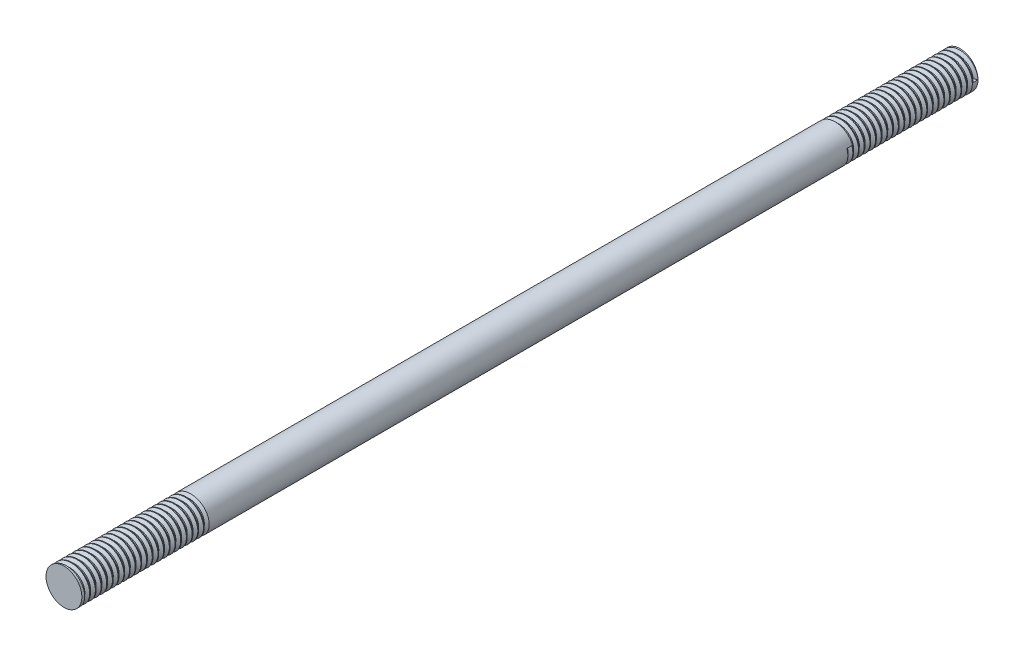
SolidWorks part; units mm, degrees
ref_plane "前视基准面" through (0, 0, 0) normal (0, 0, 1) x (1, 0, 0)
ref_plane "上视基准面" through (0, 0, 0) normal (0, 1, 0) x (1, 0, 0)
ref_plane "右视基准面" through (0, 0, 0) normal (1, 0, 0) x (0, 0, -1)
sketch "草图1" plane through (0, 0, 0) normal (0, 0, 1) x (1, 0, 0)
  circle A0 centre (0, 0) radius 1
  dimension "D1" = 2
extrude "凸台-拉伸1" add sketch "草图1" along normal blind 50
thread "螺纹线1" pitch 0.3175 method cut profile "螺纹线轮廓1" start angle 0, offset 0, length 7, pitch 0.3175, diameter 2
ref_plane "基准面4" through (1, 0, 0) normal (0, -1, 0) x (1, 0, 0)
sketch "螺纹线轮廓1" plane through (1, 0, 0) normal (0, -1, 0) x (1, 0, 0)
  line L0 (0, 0) -> (0, 0.3175) construction
  line L11 (0, 0) -> (0, 0.2778)
  line L12 (0, 0.2778) -> (-0.1719, 0.1786)
  line L13 (-0.1719, 0.1786) -> (-0.1719, 0.0992)
  line L15 (-0.1719, 0.0992) -> (0, 0)
  line L17 (-0.1719, 0.1389) -> (0, 0.1389) construction
  point P2 (0, 0)
  dimension "Pitch" = 0.3175
  dimension "Profile_Angle" = 60
  dimension "Profile_Land" = 0.0794
  dimension "Profile_Height" = 0.1719
thread "螺纹线2" pitch 0.3175 method cut profile "螺纹线轮廓2" start angle 0, offset 0, length 7, pitch 0.3175, diameter 2
ref_plane "基准面5" through (-1, 0, 50) normal (0, -1, 0) x (-1, 0, 0)
sketch "螺纹线轮廓2" plane through (-1, 0, 50) normal (0, -1, 0) x (-1, 0, 0)
  line L0 (0, 0) -> (0, 0.3175) construction
  line L11 (0, 0) -> (0, 0.2778)
  line L12 (0, 0.2778) -> (-0.1719, 0.1786)
  line L13 (-0.1719, 0.1786) -> (-0.1719, 0.0992)
  line L15 (-0.1719, 0.0992) -> (0, 0)
  line L17 (-0.1719, 0.1389) -> (0, 0.1389) construction
  point P2 (0, 0)
  dimension "Pitch" = 0.3175
  dimension "Profile_Angle" = 60
  dimension "Profile_Land" = 0.0794
  dimension "Profile_Height" = 0.1719
